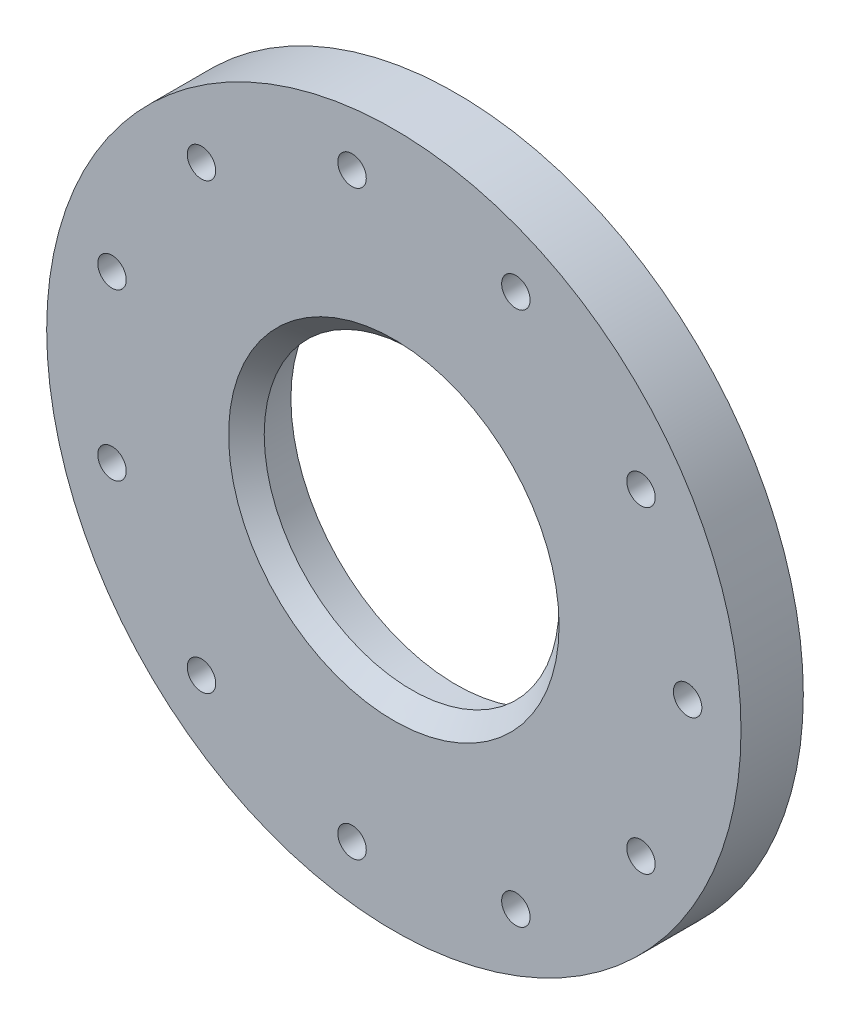
SolidWorks part; units mm, degrees
ref_plane "Front Plane" through (0, 0, 0) normal (0, 0, 1) x (1, 0, 0)
ref_plane "Top Plane" through (0, 0, 0) normal (0, 1, 0) x (1, 0, 0)
ref_plane "Right Plane" through (0, 0, 0) normal (1, 0, 0) x (0, 0, -1)
ref_plane "Plane1" through (0, 0, 15) normal (0, 0, 1) x (1, 0, 0)
sketch "Sketch1" plane through (0, 0, 15) normal (0, 0, 1) x (1, 0, 0)
  circle A0 centre (0, 0) radius 39
  circle A1 centre (0, 0) radius 33 construction
  circle A2 centre (33, 0) radius 2.5
  circle A3 centre (27.7614, -17.8411) radius 2.5
  circle A4 centre (13.7087, -30.0179) radius 2.5
  circle A5 centre (-4.6964, -32.6641) radius 2.5
  circle A6 centre (-21.6104, -24.9397) radius 2.5
  circle A7 centre (-31.6633, -9.2972) radius 2.5
  circle A8 centre (-31.6633, 9.2972) radius 2.5
  circle A9 centre (-21.6104, 24.9397) radius 2.5
  circle A10 centre (-4.6964, 32.6641) radius 2.5
  circle A11 centre (13.7087, 30.0179) radius 2.5
  circle A12 centre (27.7614, 17.8411) radius 2.5
  circle A13 centre (0, 0) radius 16.0625
  point P28 (0, 0)
extrude "Boss-Extrude1" add sketch "Sketch1" along normal blind 7
sketch "Sketch2" plane through (0, 0, 15) normal (0, 0, -1) x (-1, 0, 0)
  circle A0 centre (0, 0) radius 18.5625
  dimension "D1" = 37.125
extrude "Cut-Extrude1" cut sketch "Sketch2" against normal blind 5
sketch "Sketch3" plane through (0, 0, 22) normal (0, 0, 1) x (1, 0, 0)
  circle A0 centre (-4.6964, 32.6641) radius 1.6
  circle A1 centre (-4.6964, 32.6641) radius 2.5
  circle A2 centre (13.7087, 30.0179) radius 2.5
  circle A3 centre (13.7087, 30.0179) radius 1.6
  circle A4 centre (27.7614, 17.8411) radius 2.5
  circle A5 centre (27.7614, 17.8411) radius 1.6
  circle A6 centre (33, 0) radius 2.5
  circle A7 centre (33, 0) radius 1.6
  circle A8 centre (27.7614, -17.8411) radius 2.5
  circle A9 centre (27.7614, -17.8411) radius 1.6
  circle A10 centre (13.7087, -30.0179) radius 2.5
  circle A11 centre (13.7087, -30.0179) radius 1.6
  circle A12 centre (-4.6964, -32.6641) radius 2.5
  circle A13 centre (-4.6964, -32.6641) radius 1.6
  circle A14 centre (-21.6104, -24.9397) radius 2.5
  circle A15 centre (-21.6104, -24.9397) radius 1.6
  circle A16 centre (-31.6633, -9.2972) radius 2.5
  circle A17 centre (-31.6633, -9.2972) radius 1.6
  circle A18 centre (-31.6633, 9.2972) radius 2.5
  circle A19 centre (-31.6633, 9.2972) radius 1.6
  circle A20 centre (-21.6104, 24.9397) radius 2.5
  circle A21 centre (-21.6104, 24.9397) radius 1.6
  point P5 (0, 0)
  point P6 (1.2547, -3.0229)
  point P36 (0, 0)
  point P37 (0, 0)
  dimension "D1" = 5
  dimension "D2" = 3.2
  dimension "D3" = 11
extrude "Boss-Extrude2" add sketch "Sketch3" against normal blind 4
chamfer "Chamfer1" distance 2.5 angle 45 1 edges at (16.0625, 0, 22)
